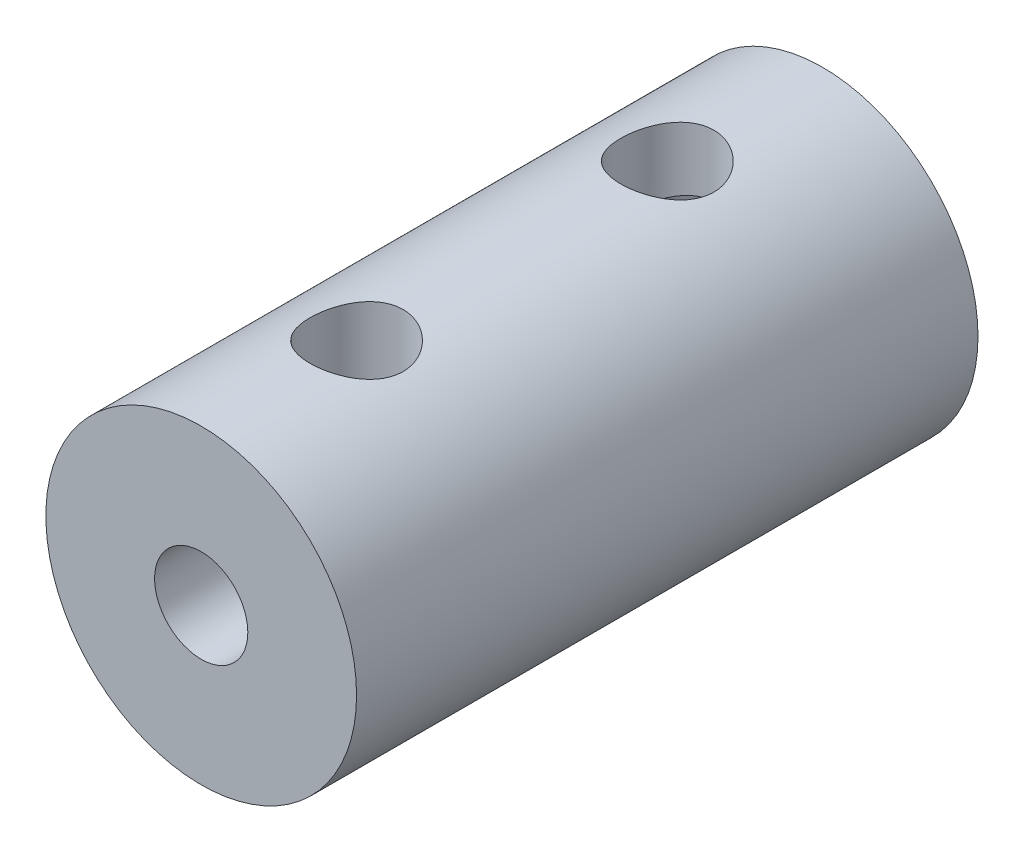
SolidWorks part; units mm, degrees
ref_plane "Front Plane" through (0, 0, 0) normal (0, 0, 1) x (1, 0, 0)
ref_plane "Top Plane" through (0, 0, 0) normal (0, 1, 0) x (1, 0, 0)
ref_plane "Right Plane" through (0, 0, 0) normal (1, 0, 0) x (0, 0, -1)
sketch "Sketch1" plane through (0, 0, 0) normal (0, 0, 1) x (1, 0, 0)
  circle A0 centre (0, 0) radius 3
  circle A1 centre (0, 0) radius 5
  dimension "D1" = 6
  dimension "D2" = 2
extrude "Boss-Extrude1" add sketch "Sketch1" along normal blind 10
sketch "Sketch2" plane through (0, 0, 10) normal (0, 0, 1) x (1, 0, 0)
  circle A0 centre (0, 0) radius 1.5
  circle A1 centre (0, 0) radius 5
  dimension "D1" = 3
extrude "Boss-Extrude2" add sketch "Sketch2" along normal blind 10
sketch "Sketch3" plane through (0, 0, 0) normal (0, 1, 0) x (1, 0, 0)
  line L0 (0, 0) -> (0, -20) construction
  line L1 (3, 0) -> (-3, 0) construction
  line L2 (-5, -20) -> (5, -20) construction
  circle A0 centre (0, -5) radius 1.5
  circle A1 centre (0, -15) radius 1.5
  dimension "D1" = 3
  dimension "D2" = 3
  dimension "D3" = 5
  dimension "D4" = 5
extrude "Cut-Extrude1" cut sketch "Sketch3" along normal blind 10
